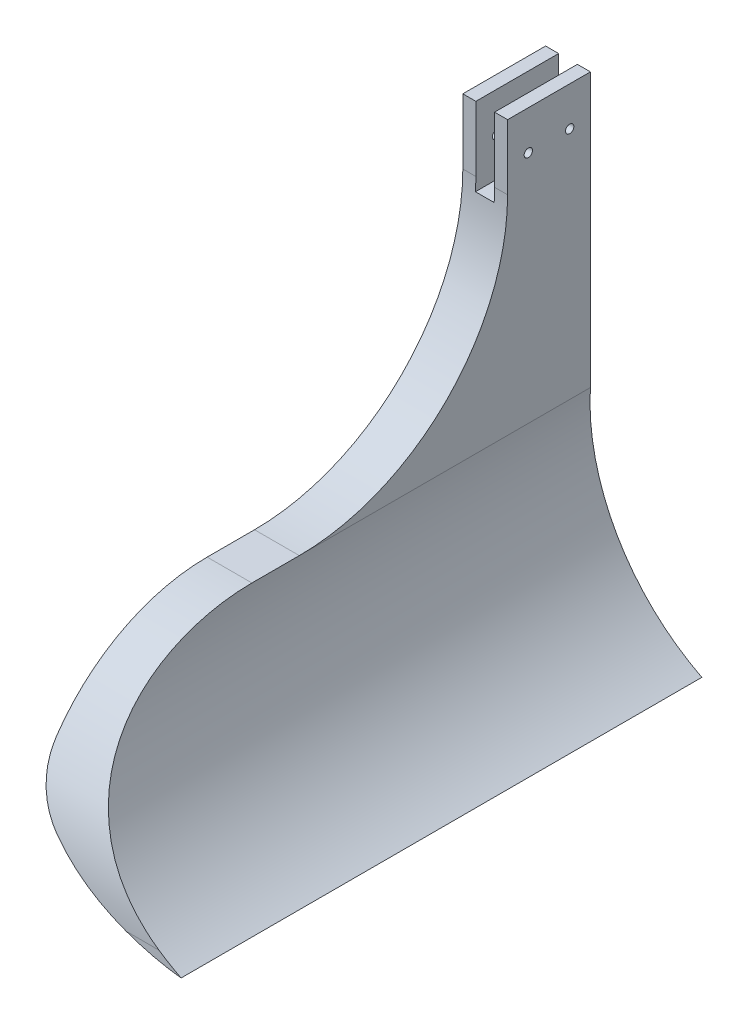
SolidWorks part; units mm, degrees
ref_plane "Plano frontal" through (0, 0, 0) normal (0, 0, 1) x (1, 0, 0)
ref_plane "Plano superior" through (0, 0, 0) normal (0, 1, 0) x (1, 0, 0)
ref_plane "Plano direito" through (0, 0, 0) normal (1, 0, 0) x (0, 0, -1)
sketch "Esboço1" plane through (0, 0, 0) normal (0, 0, 1) x (1, 0, 0)
  line L0 (-30, 75) -> (-30, 108.4013) construction
  line L1 (-25, 75) -> (-17.8, 75)
  line L2 (-30, 75) -> (-30, -42.5985)
  line L5 (-30, 75) -> (30, -75) construction
  line L6 (-30, -75) -> (30, 75) construction
  line L7 (-30, 108.4013) -> (-12.8, 108.4013) construction
  line L8 (-12.8, 108.4013) -> (-12.8, 75) construction
  line L9 (-30, 0) -> (30, 0) construction
  line L10 (-12.8, 75) -> (-12.8, 0)
  line L11 (-30, 75) -> (-30, 105)
  line L12 (-30, 105) -> (-25, 105)
  line L13 (-12.8, 105) -> (-12.8, 75)
  line L14 (-21.4, 105) -> (-21.4, 75) construction
  line L23 (-21.4, 90) -> (-25, 90) construction
  line L24 (-25, 105) -> (-25, 75)
  line L25 (-17.8, 105) -> (-17.8, 75)
  line L26 (-17.8, 105) -> (-12.8, 105)
  line L27 (-12.8, 0) -> (-30, 0)
  arc A0 (-30, -42.5985) -> (30, -75) centre (40.5019, 16.2007) ccw
  arc A1 (-12.8, 0) -> (30, -75) centre (65.6981, -4.916) ccw
  point P0 (0, 0)
  dimension "D3" = 17.2
  dimension "D4" = 30
  dimension "D1" = 150
  dimension "D2" = 60
  dimension "D5" = 3.6
extrude "Ressalto-extrusão1" add sketch "Esboço1" along normal blind 31.8 contours L27 L10 L13 L26 L25 L1 L24 L12 L11 L2 | A1 L27 L2 A0 region at (-21.4, 47.4057, 0) region at (-12.9459, -36.9962, 0)
extrude "Ressalto-extrusão2" add sketch "Esboço1<4>" along normal blind 168.2 from surface contours A1 L27 L2 A0 region at (-12.9459, -36.9962, 0) starting at face at (-17.2815, 48.9139, 31.8)
sketch "Esboço1<4>" plane through (0, 0, 0) normal (0, 0, 1) x (1, 0, 0) same geometry as "Esboço1"
fillet "Filete1" radius 80 1 edges at (-21.4, 0, 31.8)
fillet "Filete2" radius 30 1 edges at (-30, -42.5985, 100)
fillet "Filete3" radius 70 1 edges at (-21.4, 0, 200)
sketch "Esboço2" plane through (0, 0, 0) normal (1, 0, 0) x (0, 0, -1)
  line L0 (0, 0) -> (-224.9779, 0) construction
  line L1 (-200, -75) -> (-200, 0) construction
  line L2 (-190.8933, -75) -> (-190.8933, -70) construction
  line L3 (-200, -75) -> (0, -75) construction
  line L4 (-187.5392, -70) -> (-160.8933, -56.6771)
  line L5 (-200, -70) -> (0, -70) construction
  line L6 (-173.0817, -62.7713) -> (-173.7525, -61.4296) construction
  line L7 (-190.8933, -68.3229) -> (-164.2474, -55)
  line L8 (-190.8933, -70) -> (-160.8933, -55) construction
  line L9 (-187.5392, -70) -> (-160.8933, -70)
  line L10 (-190.8933, -68.3229) -> (-190.8933, -55)
  line L11 (-190.8933, -55) -> (-164.2474, -55)
  line L12 (-160.8933, -70) -> (-160.8933, -56.6771)
  line L13 (0, 105) -> (0, 0) construction
  line L14 (-31.8, 105) -> (0, 105) construction
  line L15 (-31.8, 105) -> (-31.8, 75) construction
  line L16 (-31.8, 75) -> (0, 75) construction
  line L17 (0, 105) -> (0, 75) construction
  line L18 (-15.9, 105) -> (-15.9, 75) construction
  line L19 (-31.8, 90) -> (-15.9, 90) construction
  circle A0 centre (-23.85, 90) radius 1.6
  circle A1 centre (-7.95, 90) radius 1.6
  dimension "D3" = 15
  dimension "D5" = 3.2
  dimension "D1" = 5
  dimension "D2" = 1.5
  dimension "D4" = 30
  dimension "40" = 30
extrude "Corte-extrusão2" cut sketch "Esboço2" against normal through all
sketch3d "3DSketch1"
  point P0 (-21.381, 57.0653, 0)
